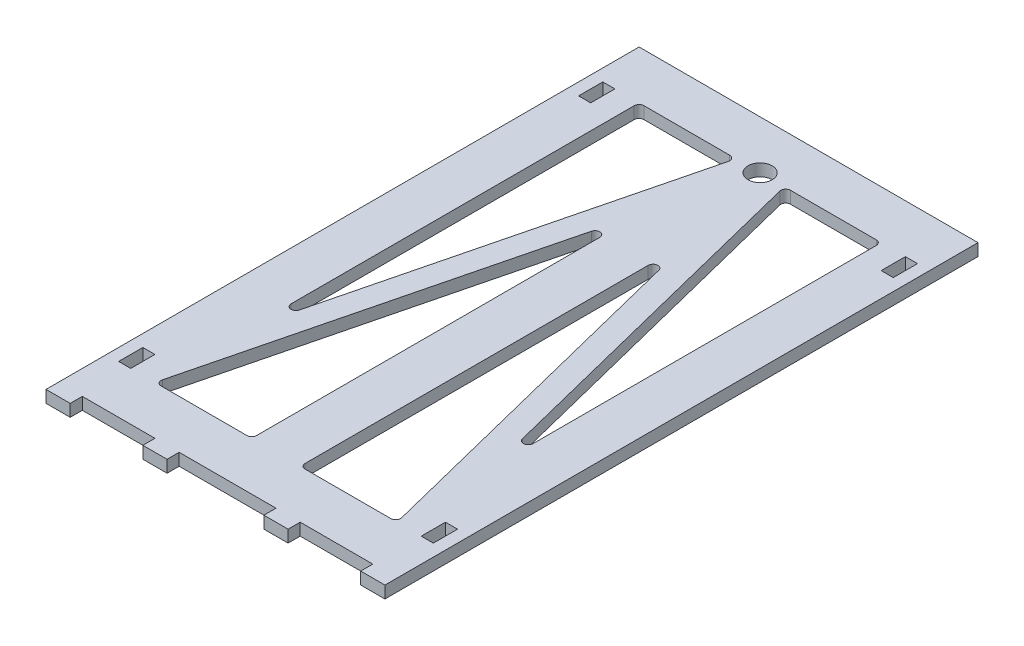
SolidWorks part; units mm, degrees
material "Beech"
ref_plane "Front Plane" through (0, 0, 0) normal (0, 0, 1) x (1, 0, 0)
ref_plane "Top Plane" through (0, 0, 0) normal (0, 1, 0) x (1, 0, 0)
ref_plane "Right Plane" through (0, 0, 0) normal (1, 0, 0) x (0, 0, -1)
sketch "Sketch1" plane through (0, 0, 0) normal (0, 1, 0) x (1, 0, 0)
  line L0 (0, 0) -> (177.8, 0)
  line L1 (0, 0) -> (0, 304.8)
  line L2 (177.8, 0) -> (177.8, 304.8)
  line L3 (0, 304.8) -> (177.8, 304.8)
  line L4 (0, 0) -> (12.7, 0)
  line L5 (0, 0) -> (0, -6.35)
  line L6 (12.7, 0) -> (12.7, -6.35)
  line L7 (0, -6.35) -> (12.7, -6.35)
  line L8 (177.8, 0) -> (165.1, 0)
  line L9 (177.8, 0) -> (177.8, -6.35)
  line L10 (165.1, 0) -> (165.1, -6.35)
  line L11 (177.8, -6.35) -> (165.1, -6.35)
  line L12 (127, 0) -> (114.3, 0)
  line L13 (127, 0) -> (127, -6.35)
  line L14 (114.3, 0) -> (114.3, -6.35)
  line L15 (127, -6.35) -> (114.3, -6.35)
  line L16 (50.8, 0) -> (63.5, 0)
  line L17 (50.8, 0) -> (50.8, -6.35)
  line L18 (63.5, 0) -> (63.5, -6.35)
  line L19 (50.8, -6.35) -> (63.5, -6.35)
  line L20 (165.1, 279.4) -> (171.45, 279.4)
  line L21 (165.1, 279.4) -> (165.1, 266.7)
  line L22 (171.45, 279.4) -> (171.45, 266.7)
  line L23 (165.1, 266.7) -> (171.45, 266.7)
  line L24 (6.35, 279.4) -> (12.7, 279.4)
  line L25 (6.35, 279.4) -> (6.35, 266.7)
  line L26 (12.7, 279.4) -> (12.7, 266.7)
  line L27 (6.35, 266.7) -> (12.7, 266.7)
  line L28 (6.35, 38.1) -> (12.7, 38.1)
  line L29 (6.35, 38.1) -> (6.35, 25.4)
  line L30 (12.7, 38.1) -> (12.7, 25.4)
  line L31 (6.35, 25.4) -> (12.7, 25.4)
  line L32 (165.1, 38.1) -> (171.45, 38.1)
  line L33 (165.1, 38.1) -> (165.1, 25.4)
  line L34 (171.45, 38.1) -> (171.45, 25.4)
  line L35 (165.1, 25.4) -> (171.45, 25.4)
  line L36 (101.6, 279.4) -> (152.4, 279.4)
  line L37 (152.4, 279.4) -> (152.4, 76.2)
  line L38 (152.4, 76.2) -> (101.6, 279.4)
  line L39 (101.6, 228.6) -> (101.6, 25.4)
  line L40 (101.6, 25.4) -> (152.4, 25.4)
  line L41 (152.4, 25.4) -> (101.6, 228.6)
  line L42 (76.2, 279.4) -> (25.4, 279.4)
  line L43 (25.4, 279.4) -> (25.4, 76.2)
  line L44 (25.4, 76.2) -> (76.2, 279.4)
  line L45 (76.2, 228.6) -> (76.2, 25.4)
  line L46 (76.2, 25.4) -> (25.4, 25.4)
  line L47 (25.4, 25.4) -> (76.2, 228.6)
  circle A0 centre (88.9, 279.4) radius 6.35
  point P21 (88.9, 304.8)
  dimension "D8" = 12.7
  dimension "D1" = 177.8
  dimension "D2" = 6.35
  dimension "D3" = 12.7
  dimension "D4" = 50.8
  dimension "D5" = 50.8
  dimension "D6" = 304.8
  dimension "D7" = 25.4
  dimension "D9" = 25.4
  dimension "D10" = 25.4
  dimension "D11" = 12.7
  dimension "D12" = 12.7
  dimension "D13" = 203.2
  dimension "D14" = 50.8
  dimension "D15" = 50.8
extrude "Front Panel" add sketch "Sketch1" along normal blind 6.35 contours L3 L1 L0 L2 A0 L35 L33 L32 L34 L31 L29 L28 L30 L27 L25 L24 L26 L23 L21 L20 L22 | L5 L7 L6 L0 | L17 L19 L18 L0 | L15 L13 L0 L14 | L11 L9 L0 L10 region at (88.9, 0, -151.9139) region at (6.35, 0, 3.175) region at (57.15, 0, 3.175) region at (171.45, 0, 3.175) region at (120.65, 0, 3.175)
fillet "Fillet1" radius 2.54 12 edges at (25.4, 3.175, -76.2) (152.4, 3.175, -76.2) (25.4, 3.175, -25.4) (76.2, 3.175, -25.4) (101.6, 3.175, -25.4) (152.4, 3.175, -25.4) (76.2, 3.175, -228.6) (101.6, 3.175, -228.6) (25.4, 3.175, -279.4) (76.2, 3.175, -279.4) (101.6, 3.175, -279.4) (152.4, 3.175, -279.4)
equation "\"CageLeftBottomEdge\"=22.11mm"
equation "\"CageLeftTopEdge\"=22.11mm"
equation "\"CageRightBottomEdge\"=21.63mm"
equation "\"CageRightTopEdge\"=21.63mm"
equation "\"CageHeight\"=86.04mm"
equation "\"CageLength\"=73.76mm"
equation "\"CageTopScrewClearance\"=10mm"
equation "\"CageBottomScrewClearance\"=25mm"
equation "\"CageLeftTopDepth\"= 11.65mm"
equation "\"CageLeftBottomDepth\"=11.11mm"
equation "\"CageLeftTopHeight\"=8.56175mm"
equation "\"CageLeftBottomHeight\"=16mm"
equation "\"CageRightTopDepth\"= 11.05mm"
equation "\"CageRightBottomDepth\"=10.58mm"
equation "\"CageRightTopHeight\"=9.6mm"
equation "\"CageRightBottomHeight\"=15.49mm"
equation "\"CageLeftTopChannelDepth\"=2.41908mm"
equation "\"CageLeftBottomChannelDepth\"=2.588mm"
equation "\"CageLeftChannelHeight\"=11.7mm"
equation "\"CageRightTopChannelDepth\"=2.32mm"
equation "\"CageRightBottomChannelDepth\"=2.318mm"
equation "\"CageRightChannelHeight\"=10mm"
equation "\"CageChanRelHeight\"=23.99mm"
equation "\"CageChanRelDepth\"=5.492mm"
equation "\"CageChamberRadius\"=16.261mm"
equation "\"CageScrewDiameter\"=4.8mm"
equation "\"CageSetScrewDiameter\"=3.5mm"
equation "\"CageAxleRadius\"=6.639mm"
equation "\"CageAxleKeyHeight\"=1.619mm"
equation "\"CageAxleKeyWidth\"=2.662mm"
equation "\"CageHoseWindowWidth\"=16.29mm"
equation "\"CageHoseWindowHeight\"=26.5mm"
equation "\"CageHoseWindow-Edge\"=8.89mm"
equation "\"CageScrew-VerticalEdge\"=5.0mm"
equation "\"CageScrew-HorizontalEdge\"=7.5mm"
equation "\"CageScrew-HoseCornerScrewEdge\"=4.45mm"
equation "\"CageAxle-BottomEdge\"=56.05mm"
equation "\"CageAxle-FrontEdge\"=46.03mm"
equation "\"CageBackSetScrew-Axle\"=40mm"
equation "\"CageFrontSetScrew-Axle\"=22mm"
equation "\"CageVelocityWindow-BackEdge\"=34.8mm"
equation "\"CageVelocityWindow-BottomEdge\"=27.55mm"
equation "\"CageVelocityWindowHeight\"=22.29mm"
equation "\"CageVelocityWindowWidth\"=12.61mm"
equation "\"TriggerSlot-BottomEdge\"=6.35mm"
equation "\"TriggerSlot-FrontEdge\"=15mm"
equation "\"TriggerSlotSize\"=6.7mm"
equation "\"TriggerRackOffset\"=6mm"
equation "\"TriggerSlotSizeInt\"=.25in"
equation "\"MotorMountLegLength\"=.25in"
equation "\"GearOffset\"=.264907in"
equation "\"TriggerSlotSpacing\"=.25in"
equation "\"TriggerMiniSlotWidth\"=3.5mm"
equation "\"TriggerRackWidth\"=6.5mm"
equation "\"pandiscradius\"=14in"
equation "\"towermaterialwidth\"=.25in"
equation "\"towerslotlength\"=.5in"
equation "\"towermarkerspace\"=5in"
equation "\"towerslothorizoffset\"=1in"
equation "\"towerslothorizspacing\"=2in"
equation "\"towerslotvertoffset\"=3in"
equation "\"towerslotvertspacing\"=1in"
equation "\"towerheight\"=12in"
equation "\"towerupslot\"=1in"
equation "\"D1@Sketch1\"=(\"towerslothorizoffset\"+\"towerslothorizspacing\"+\"towerslotlength\")*2"
equation "\"D2@Sketch1\"=\"towermaterialwidth\""
equation "\"D3@Sketch1\"=\"towerslotlength\""
equation "\"D4@Sketch1\"=\"towerslothorizspacing\""
equation "\"D5@Sketch1\"=\"towerslothorizspacing\""
equation "\"D6@Sketch1\"=\"towerheight\""
equation "\"D7@Sketch1\"=\"towerupslot\""
equation "\"toweraxle\"=.5in"
equation "\"D8@Sketch1\"=\"toweraxle\""
equation "\"D9@Sketch1\"=\"towerupslot\""
equation "\"D10@Sketch1\"= \"towerupslot\""
equation "\"D1@Front Panel\"=\"towermaterialwidth\""
equation "\"stepperouterrad\"=10mm"
equation "\"stepperscrewsize\"=3.45mm"
equation "\"stepperscrewc2c\"=49.5mm"
equation "\"stepperdepthoffset\"=24mm"
equation "\"stepperhorizoffset\"=22.91mm"
equation "\"shaftslotOD\"=18.8mm"
equation "\"shaftslotID\"=13.28mm"
equation "\"shaftkeywidth\"=2.67mm"
equation "\"shaftkeydepth\"=1.8mm"
equation "\"shaftcollartotaldepth\"=12.5mm"
equation "\"shaftsquaredepth\"=6mm"
equation "\"shaftsetscrewsize\"=3.5mm"
equation "\"shaftkeytightdepth\"=1.85mm"
equation "\"shaftslottightID\"=12.78mm"
equation "\"shaftsetscrewoffset\"=9mm"
equation "\"cagecollartotaldepth\"=10mm"
equation "\"cagecollartotalwidth\"=35mm"
equation "\"cagecollarbasedepth\"=4mm"
equation "\"D11@Sketch1\"=\"toweraxle\""
equation "\"D12@Sketch1\"=\"toweraxle\""
equation "\"towerspeedwidth\"=2in"
equation "\"D15@Sketch1\"=\"towerspeedwidth\""
equation "\"towerspeedheight\"=8in"
equation "\"D13@Sketch1\"=\"towerspeedheight\""
equation "\"towerspeedgap\"=2in"
equation "\"D14@Sketch1\"=\"towerspeedgap\""
equation "\"gearhubintdiam\"=30mm"
equation "\"gearhubintwid\"=15mm"
equation "\"stepperaxleflat\"=.037in"
equation "\"stepperaxlerad\"=0.11811024in"
equation "\"ajaxaxlesize\"=3.87mm"
equation "\"ajaxinnercut\"=2.3mm"
equation "\"ajaxwidth\"=6.1mm"
equation "\"ajaxdiametral\"=25.8854"
equation "\"ajaxcutoutdepth\"=2.3mm"
equation "\"ajax4020gap\"=29.5mm"
equation "\"ajax4010gap\"=24.5mm"
equation "\"ajax20hubbuffer\"=6.1mm"
equation "\"ajax20hubholeoffset\"=.19685in"
equation "\"ajax20hubholesize\"=.059055in"
equation "\"ajax20cutoutint\"=13.4mm"
equation "\"ajax40hubholesize\"=7.21mm"
equation "\"ajax40hubholeoffset\"=10mm"
equation "\"ajax40hubbuffer\"=8.9mm"
equation "\"ajax40cutoutint\"=32.6mm"
equation "\"bearingpandiscrad\"=6.8in"
equation "\"bearingpandiscang\"=48.75deg"
equation "\"bearingclearholedist\"=4.7345in"
equation "\"bearingclearholesize\"=.5in"
equation "\"bearingclearholeang\"=22.5deg"
equation "\"bearingmountholedist\"=4.25in"
equation "\"bearingwirehole\"=1.5in"
equation "\"no6diam\"=.146in"
equation "\"shortconangle\"=20deg"
equation "\"shortconlen\"=.875in"
equation "\"longconlen\"=1.25in"
equation "\"longconangle\"=15deg"
